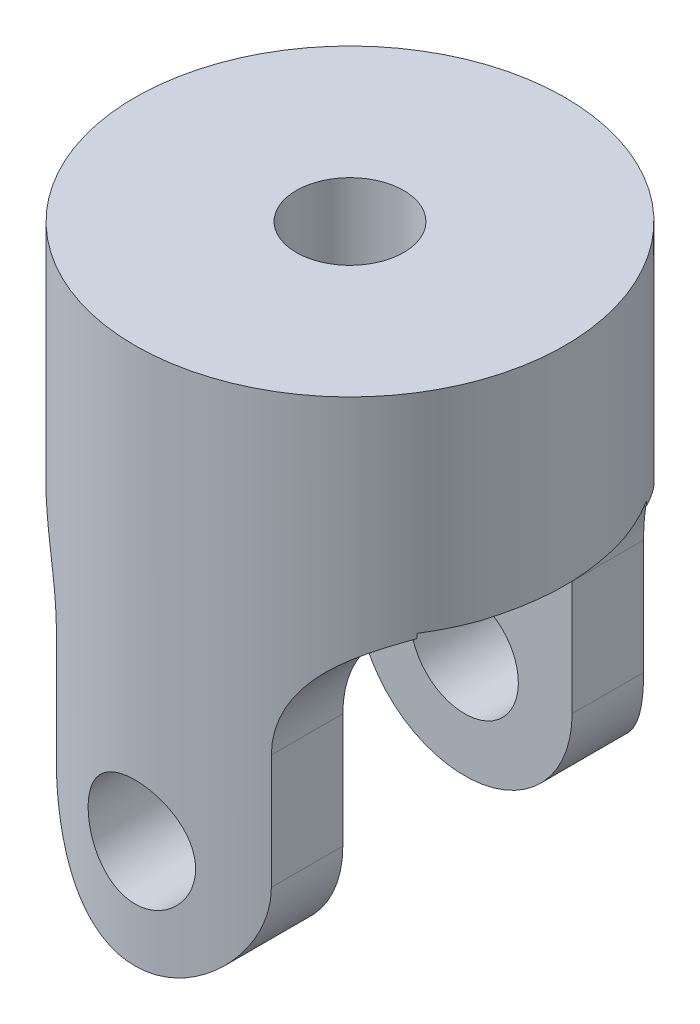
SolidWorks part; units mm, degrees
note: '?' marks a value the reader was unsure of.
ref_plane "Front" through (0, 0, 0) normal (0, 0, 1) x (1, 0, 0)
ref_plane "Top" through (0, 0, 0) normal (0, 1, 0) x (-1, 0, 0)
ref_plane "Right" through (0, 0, 0) normal (1, 0, 0) x (0, 0, -1)
sketch "Sketch1" plane through (0, 0, 0) normal (0, 1, 0) x (-1, 0, 0)
  circle A0 centre (0, 0) radius 19.05
  dimension "D1" = 38.1
extrude "Base-Extrude" add sketch "Sketch1" along normal blind 47.625
sketch "Sketch2" plane through (0, 0, 0) normal (0, 0, 1) x (1, 0, 0)
  line L0 (0, 0) -> (0, 23.7435) construction
  line L1 (9.525, 9.525) -> (9.525, 19.685)
  line L2 (-9.525, 9.525) -> (-9.525, 19.685)
  line L3 (19.05, 29.21) -> (19.05, 0)
  line L4 (-19.05, 47.625) -> (-19.05, 0) construction
  line L5 (-19.05, 0) -> (-19.05, 29.21)
  line L6 (19.05, 0) -> (-19.05, 0) construction
  arc A0 (-9.525, 9.525) -> (9.525, 9.525) centre (0, 9.525) ccw
  arc A1 (9.525, 19.685) -> (19.05, 29.21) centre (19.05, 19.685) cw
  arc A2 (-9.525, 19.685) -> (-19.05, 29.21) centre (-19.05, 19.685) ccw
  dimension "D3" = 9.525
  dimension "D2" = 19.05
  dimension "D4" = 29.21
extrude "Cut-Extrude1" cut sketch "Sketch2" against normal through all and the other way through all flip side to cut
sketch "Sketch8" plane through (0, 0, 0) normal (1, 0, 0) x (0, 0, -1)
  line L0 (-19.05, 0) -> (19.05, 0) construction
  line L1 (-10.16, 0) -> (-10.16, 29.1452)
  line L2 (10.16, 29.1452) -> (-10.16, 29.1452)
  line L3 (10.16, 29.1452) -> (10.16, 0)
  line L4 (0, 0) -> (0, 14.3858) construction
  point P4 (0, 0)
  dimension "D1" = 29.1452
  dimension "D2" = 20.32
extrude "Cut-Extrude5" cut sketch "Sketch8" against normal through all and the other way through all flip side to cut
sketch "Sketch11" plane through (0, 0, 0) normal (0, 0, 1) x (1, 0, 0)
  circle A0 centre (0, 9.525) radius 4.7625
  dimension "D1" = 9.525
extrude "Cut-Extrude6" cut sketch "Sketch11" against normal through all and the other way through all
sketch "Sketch12" plane through (0, 47.625, 0) normal (0, 1, 0) x (-1, 0, 0)
  circle A0 centre (0, 0) radius 4.7625
  dimension "D1" = 9.525
extrude "Cut-Extrude7" cut sketch "Sketch12" against normal through all
ref_axis "Axis1" through (0, 97.625, 0) along (0, -1, 0)?
